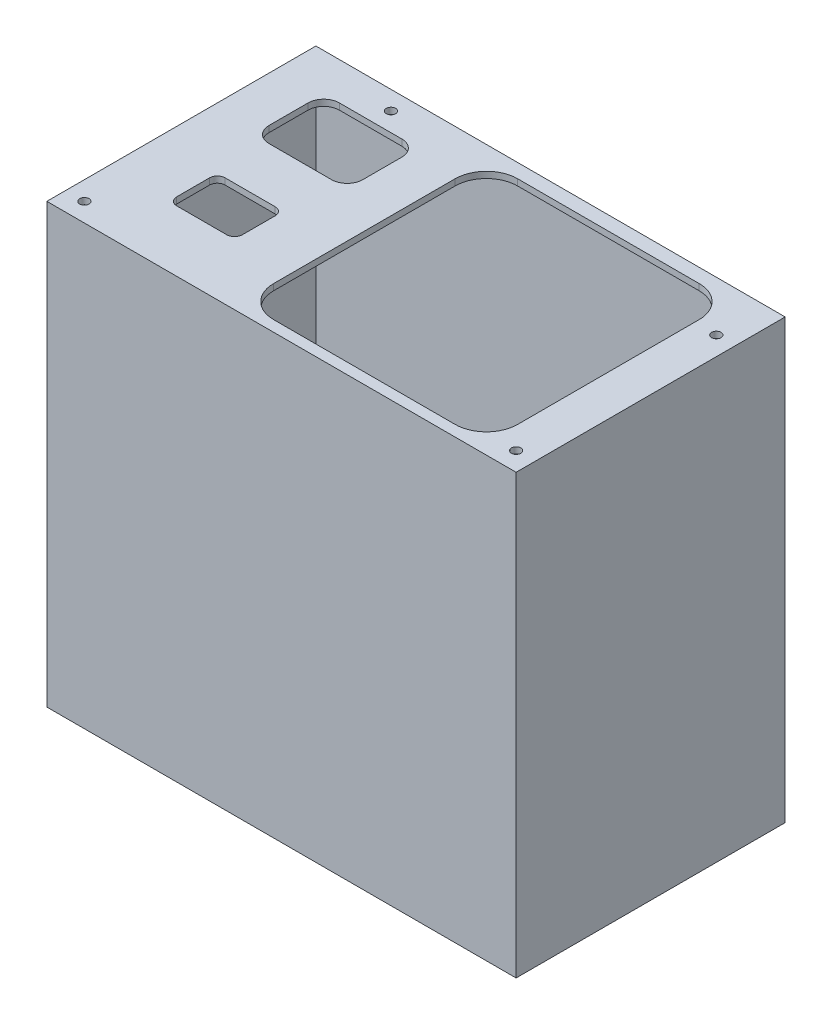
SolidWorks part; units mm, degrees
ref_plane "Front Plane" through (0, 0, 0) normal (0, 0, 1) x (1, 0, 0)
ref_plane "Top Plane" through (0, 0, 0) normal (0, 1, 0) x (1, 0, 0)
ref_plane "Right Plane" through (0, 0, 0) normal (1, 0, 0) x (0, 0, -1)
sketch "Sketch1" plane through (0, 0, 0) normal (0, 1, 0) x (1, 0, 0)
  line L1 (-75, 43) -> (75, 43)
  line L2 (-75, 43) -> (-75, -43)
  line L3 (-75, -43) -> (75, -43)
  line L4 (75, 43) -> (75, -43)
  line L5 (-75, 43) -> (75, -43) construction
  line L6 (-75, -43) -> (75, 43) construction
  point P0 (0, 0)
  dimension "D1" = 86
  dimension "D2" = 150
extrude "Boss-Extrude1" add sketch "Sketch1" along normal blind 140
sketch "Sketch2" plane through (0, 140, 0) normal (0, 1, 0) x (1, 0, 0)
  line L0 (-75, -43) -> (75, -43) construction
  line L1 (-75, 43) -> (-75, -43) construction
  line L2 (75, -43) -> (75, 43) construction
  line L3 (75, 43) -> (-75, 43) construction
  line L5 (62, -39.5) -> (-16, -39.5)
  line L6 (62, -39.5) -> (62, 38.5)
  line L7 (62, 38.5) -> (-16, 38.5)
  line L8 (-16, -39.5) -> (-16, 38.5)
  line L9 (62, -39.5) -> (-16, 38.5) construction
  line L10 (62, 38.5) -> (-16, -39.5) construction
  line L11 (-30.5, 8.5) -> (-60.5, 8.5)
  line L12 (-30.5, 8.5) -> (-30.5, 31)
  line L13 (-30.5, 31) -> (-60.5, 31)
  line L14 (-60.5, 8.5) -> (-60.5, 31)
  line L15 (-30.5, 8.5) -> (-60.5, 31) construction
  line L16 (-30.5, 31) -> (-60.5, 8.5) construction
  line L17 (-34.5, -23.5) -> (-55.5, -23.5)
  line L18 (-34.5, -23.5) -> (-34.5, -8)
  line L19 (-34.5, -8) -> (-55.5, -8)
  line L20 (-55.5, -23.5) -> (-55.5, -8)
  line L21 (-34.5, -23.5) -> (-55.5, -8) construction
  line L22 (-34.5, -8) -> (-55.5, -23.5) construction
  circle A0 centre (69, -37) radius 1.5
  circle A1 centre (69, 27) radius 1.5
  circle A2 centre (-69, -37) radius 1.5
  circle A3 centre (-45, 37) radius 1.5
  point P16 (23, -0.5)
  point P21 (-45.5, 19.75)
  point P26 (-45, -15.75)
  dimension "D1" = 3
  dimension "D2" = 3
  dimension "D3" = 3
  dimension "D4" = 3
  dimension "D5" = 6
  dimension "D6" = 6
  dimension "D7" = 6
  dimension "D8" = 6
  dimension "D9" = 6
  dimension "D10" = 16
  dimension "D11" = 6
  dimension "D12" = 30
  dimension "D13" = 78
  dimension "D14" = 78
  dimension "D15" = 3.5
  dimension "D16" = 13
  dimension "D17" = 30
  dimension "D18" = 22.5
  dimension "D19" = 21
  dimension "D20" = 15.5
  dimension "D21" = 12
  dimension "D22" = 14.5
  dimension "D23" = 16.5
  dimension "D24" = 19.5
  dimension "D25" = 5
  dimension "D26" = 4
extrude "Cut-Extrude1" cut sketch "Sketch2" against normal blind 2
shell "Shell4" thickness 1
fillet "Fillet1" radius 10 4 edges at (-16, 139, 39.5) (62, 139, 39.5) (62, 139, -38.5) (-16, 139, -38.5)
fillet "Fillet2" radius 5 4 edges at (-60.5, 139, -31) (-60.5, 139, -8.5) (-30.5, 139, -8.5) (-30.5, 139, -31)
fillet "Fillet3" radius 2.5 4 edges at (-34.5, 139, 8) (-34.5, 139, 23.5) (-55.5, 139, 23.5) (-55.5, 139, 8)
equation "\"`15\"=108.015"
